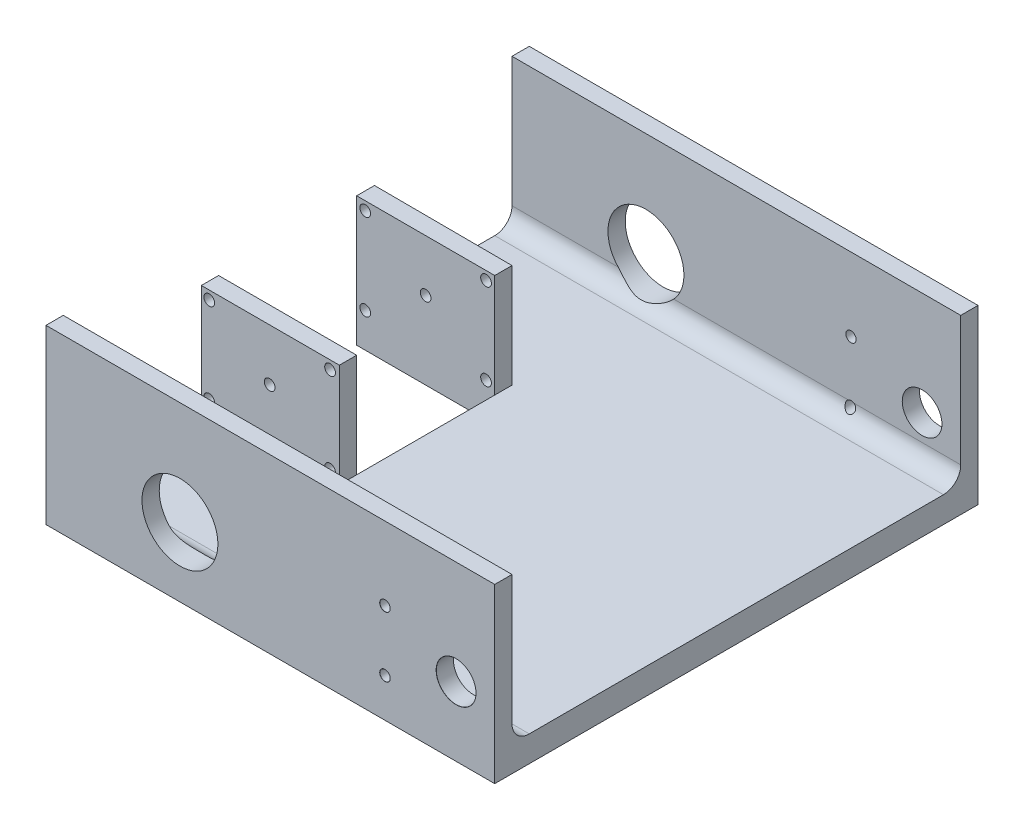
SolidWorks part; units mm, degrees
ref_plane "Front Plane" through (0, 0, 0) normal (0, 0, 1) x (1, 0, 0)
ref_plane "Top Plane" through (0, 0, 0) normal (0, 1, 0) x (1, 0, 0)
ref_plane "Right Plane" through (0, 0, 0) normal (1, 0, 0) x (0, 0, -1)
sketch "Sketch2" plane through (0, 0, 0) normal (0, 1, 0) x (1, 0, 0)
  line L0 (-65, 65) -> (-65, 70)
  line L1 (-65, 65) -> (65, 65)
  line L2 (-65, 65) -> (-65, -65)
  line L3 (-65, -65) -> (65, -65)
  line L4 (65, 65) -> (65, -65)
  line L5 (-65, 65) -> (65, -65) construction
  line L6 (-65, -65) -> (65, 65) construction
  line L7 (65, 70) -> (-65, 70)
  line L8 (65, 70) -> (65, 65)
  line L9 (-71.5, 0) -> (71.5, 0) construction
  line L10 (65, -70) -> (65, -65)
  line L11 (65, -70) -> (-65, -70)
  line L12 (-65, -65) -> (-65, -70)
  line L13 (-65, 20) -> (-65, 25.1643)
  line L14 (-65, -20) -> (-25, -20)
  line L15 (-65, -20) -> (-65, 20)
  line L16 (-65, 20) -> (-25, 20)
  line L17 (-25, -20) -> (-25, 20)
  line L18 (-65, -20) -> (-25, 20) construction
  line L19 (-65, 20) -> (-25, -20) construction
  line L20 (-25, 25) -> (-25.6854, 25.6854)
  line L21 (-65, -20) -> (-65, -25.1343)
  point P0 (0, 0)
  point P12 (-45, 0)
  dimension "D1" = 130
  dimension "D2" = 130
  dimension "D3" = 5
  dimension "D4" = 40
  dimension "D5" = 40
  dimension "D6" = 110
extrude "Boss-Extrude1" add sketch "Sketch2" along normal blind 7.5 contours L4 L1 L2 L3 region at (4.7059, 0, 0)
extrude "Boss-Extrude2" add sketch "Sketch2<4>" along normal blind 50 contours L3 L12 L11 L10 | L8 L7 L0 L1 region at (0, 0, -67.5) region at (0, 0, 67.5)
sketch "Sketch2<4>" plane through (0, 0, 0) normal (0, 1, 0) x (1, 0, 0) same geometry as "Sketch2"
sketch "Sketch5" plane through (0, 0, 70) normal (0, 0, 1) x (1, 0, 0)
  line L0 (-65, 20) -> (65, 20) construction
  line L1 (33.2, 11.25) -> (33.2, 28.75) construction
  line L4 (-65, 50) -> (-65, 0) construction
  line L5 (65, 50) -> (65, 0) construction
  line L6 (65, 0) -> (-65, 0) construction
  point P8 (-26.2, 20)
  point P11 (33.2, 20)
  point P12 (33.2, 28.75)
  point P13 (33.2, 11.25)
  point P14 (53.8, 20)
  dimension "D1" = 20
  dimension "D2" = 17.5
  dimension "D3" = 11.2
  dimension "D4" = 31.8
  dimension "D5" = 80
other "AlignGroup1"
other "AlignGroup2"
sketch "Sketch8" plane through (0, 0, 70) normal (0, 0, 1) x (1, 0, 0)
  point P0 (33.2, 28.75)
  point P3 (33.2, 11.25)
hole_wizard "Ø3.0mm Dowel Hole1" positions "Sketch8" profile "Sketch7" hole size "Ø3.0" standard "DIN" end condition through all
sketch "Sketch7" plane through (33.2, 28.75, 70) normal (1, 0, 0) x (0, -1, 0)
  line L0 (0, 0) -> (0, 140)
  line L1 (0, 140) -> (1.5, 140)
  line L2 (1.5, 140) -> (1.5, 0.025)
  line L3 (1.5, 0.025) -> (1.525, 0)
  line L5 (1.525, 0) -> (0, 0)
  line L6 (-1.5, 0.025) -> (-1.525, 0) construction
  line L11 (0, -6.35) -> (0, 107.95) construction
  dimension "Thru Hole Dia." = 3
  dimension "Thru Hole Depth" = 140
  dimension "Near C'Sink Dia." = 3.05
  dimension "Near C'Sink Angle" = 90
fillet "Fillet1" radius 5 2 edges at (0, 7.5, 65) (0, 7.5, -65)
hole_wizard "Ø11.5 (11.5) Diameter Hole2" positions "3DSketch2" profile "Sketch10" hole size "Ø11.5" standard "ANSI Metric" end condition through all
sketch3d "3DSketch2"
  point P0 (53.8, 20, 70)
sketch "Sketch10" plane through (53.8, 20, 70) normal (1, 0, 0) x (0, -1, 0)
  line L0 (0, 0) -> (0, 140)
  line L1 (0, 140) -> (5.75, 140)
  line L2 (5.75, 140) -> (5.75, 0.025)
  line L3 (5.75, 0.025) -> (5.775, 0)
  line L5 (5.775, 0) -> (0, 0)
  line L6 (-5.75, 0.025) -> (-5.775, 0) construction
  line L11 (0, -6.35) -> (0, 107.95) construction
  dimension "Thru Hole Dia." = 11.5
  dimension "Thru Hole Depth" = 140
  dimension "Near C'Sink Dia." = 11.55
  dimension "Near C'Sink Angle" = 90
hole_wizard "Ø1.0 (22) Diameter Hole1" positions "3DSketch3" profile "Sketch12" hole size "Ø1.0" standard "ANSI Metric"
sketch3d "3DSketch3"
  point P0 (-26.2, 20, 70)
sketch "Sketch12" plane through (-26.2, 20, 70) normal (1, 0, 0) x (0, -1, 0)
  line L0 (0, 0) -> (0, 146.6095)
  line L1 (0, 146.6095) -> (11, 140)
  line L2 (11, 140) -> (11, 0)
  line L5 (11, 0) -> (0, 0)
  line L10 (0, 146.6095) -> (-11, 140) construction
  line L11 (0, -6.35) -> (0, 107.95) construction
  dimension "Hole Dia." = 22
  dimension "Hole Depth" = 140
  dimension "Drill Angle" = 118
sketch "Sketch16" plane through (0, 7.5, 0) normal (0, 1, 0) x (1, 0, 0)
  line L0 (-65, 20) -> (-65, 25.1643)
  line L1 (-25, 25) -> (-65, 25.1643)
  line L2 (-25, 25) -> (-25, 20)
  line L3 (-65, -20) -> (-65, -25)
  line L4 (-65, -20) -> (-65, -60) construction
  line L5 (-65, -25) -> (-25, -25)
  line L6 (-25, -25) -> (-25, -20)
  line L7 (-65, -20) -> (-25, -20) construction
  line L8 (-65, -20) -> (-25, -20) construction
  line L9 (-65, -20) -> (-25, -20)
  line L10 (-65, 20) -> (-25, 20)
  dimension "D1" = 5
  dimension "D2" = 40
  dimension "D3" = 5
extrude "Boss-Extrude3" add sketch "Sketch16" along normal blind 30
sketch "Sketch18" plane through (0.1022, 0, -24.8969) normal (0.0041, 0, -1) x (-1, 0, -0.0041)
  line L0 (25.1025, 22.5) -> (65.1028, 22.5) construction
  line L3 (25.1025, 37.5) -> (25.1025, 7.5) construction
  line L4 (25.1025, 7.5) -> (65.1028, 7.5) construction
  line L5 (45.1026, 7.5) -> (45.1026, 37.5) construction
  line L6 (25.1025, 37.5) -> (65.1028, 37.5) construction
  line L7 (65.1028, 37.5) -> (65.1028, 7.5) construction
  line L9 (27.6026, 35) -> (62.6026, 35) construction
  line L10 (27.6026, 35) -> (27.6026, 10) construction
  line L11 (27.6026, 10) -> (62.6026, 10) construction
  line L12 (62.6026, 35) -> (62.6026, 10) construction
  line L13 (27.6026, 35) -> (62.6026, 10) construction
  line L14 (27.6026, 10) -> (62.6026, 35) construction
  point P6 (45.1026, 22.5)
  point P18 (27.6026, 35)
  point P19 (62.6026, 35)
  point P20 (62.6026, 10)
  point P21 (27.6026, 10)
  point P25 (45.1026, 22.5)
  dimension "D1" = 25
  dimension "D2" = 35
hole_wizard "Ø3.1 (3.1) Diameter Hole1" positions "Sketch18" profile "Sketch20" hole size "Ø3.1" standard "ANSI Metric"
sketch "Sketch20" plane through (-45, 22.5, -25.0821) normal (0, 1, 0) x (-1, 0, -0.0041)
  line L0 (0, 0) -> (0, 51.0962)
  line L1 (0, 51.0962) -> (1.55, 50.1648)
  line L2 (1.55, 50.1648) -> (1.55, 0.025)
  line L3 (1.55, 0.025) -> (1.575, 0)
  line L5 (1.575, 0) -> (0, 0)
  line L6 (-1.55, 0.025) -> (-1.575, 0) construction
  line L10 (0, 51.0962) -> (-1.55, 50.1648) construction
  line L11 (0, -6.35) -> (0, 107.95) construction
  dimension "Hole Dia." = 3.1
  dimension "Hole Depth" = 50.1648
  dimension "Near C'Sink Dia." = 3.15
  dimension "Near C'Sink Angle" = 90
  dimension "Drill Angle" = 118
